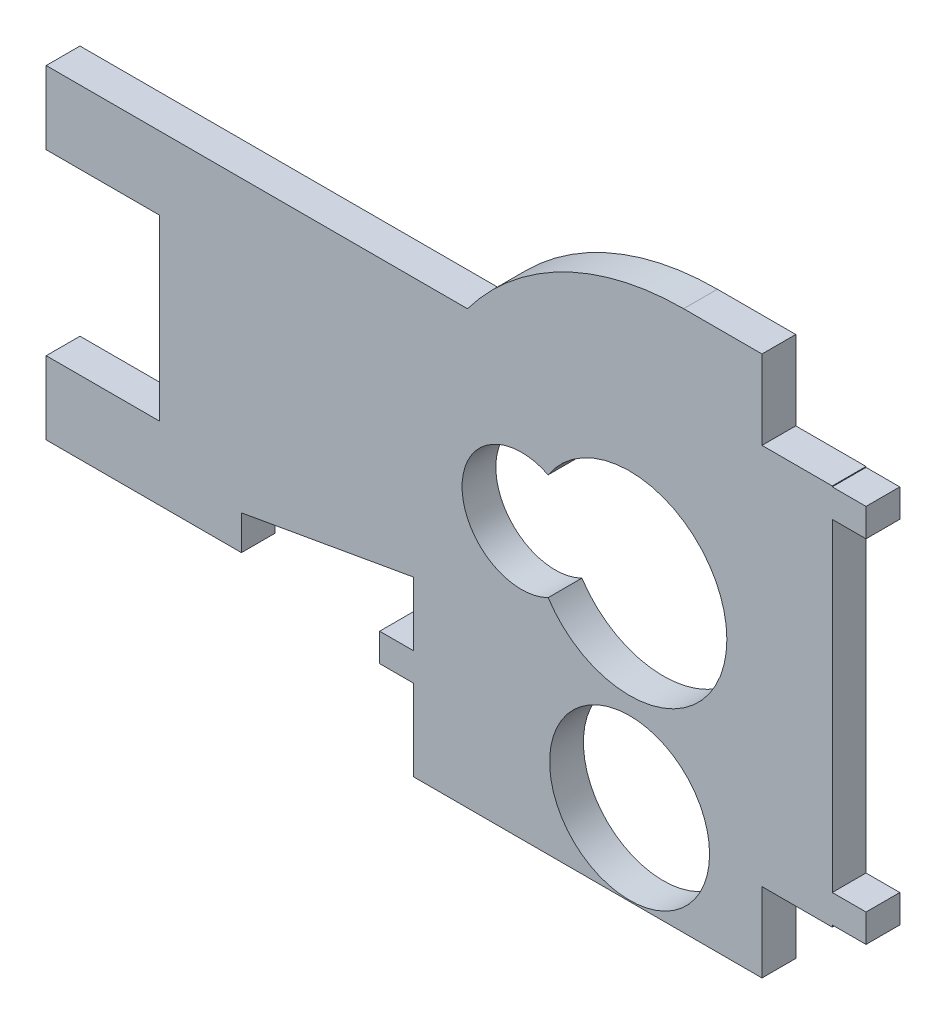
SolidWorks part; units mm, degrees
material "Balsa"
ref_plane "Front Plane" through (0, 0, 0) normal (0, 0, 1) x (1, 0, 0)
ref_plane "Top Plane" through (0, 0, 0) normal (0, 1, 0) x (1, 0, 0)
ref_plane "Right Plane" through (0, 0, 0) normal (1, 0, 0) x (0, 0, -1)
sketch "Sketch1" plane through (0, 0, 0) normal (0, 0, 1) x (1, 0, 0)
  line L0 (0, -1000.1535) -> (0, 48999.8465) construction
  line L1 (0, 9.144) -> (-5.08, 9.144) construction
  line L2 (-1000, 0) -> (49000, 0) construction
  line L3 (9.525, 16.51) -> (11.1125, 16.51)
  line L4 (2.54, 21.59) -> (9.525, 21.59)
  line L5 (-10.16, 8.89) -> (-10.16, -3.81)
  line L6 (-10.16, -3.81) -> (9.525, -3.81)
  line L7 (9.525, 21.59) -> (9.525, -3.81)
  line L8 (-11.7475, 0) -> (-10.16, 0)
  line L9 (-11.7475, 0) -> (-11.7475, 1.3208)
  line L10 (-11.7475, 1.3208) -> (-10.16, 1.3208)
  line L11 (-10.16, 0) -> (-10.16, 1.3208)
  line L12 (9.525, 0) -> (11.1125, 0)
  line L13 (9.525, 0) -> (9.525, 1.3208)
  line L14 (9.525, 1.3208) -> (11.1125, 1.3208)
  line L15 (11.1125, 0) -> (11.1125, 1.3208)
  line L16 (9.525, 16.51) -> (9.525, 17.8308)
  line L17 (9.525, 17.8308) -> (11.1125, 17.8308)
  line L18 (11.1125, 16.51) -> (11.1125, 17.8308)
  line L19 (-7.62, 16.51) -> (-27.4189, 16.51)
  line L20 (-27.4189, 16.51) -> (-27.4189, 1.27)
  line L21 (-27.4189, 1.27) -> (-10.16, 4.318)
  line L22 (9.525, 8.89) -> (-35.5862, 8.89) construction
  line L23 (-27.4189, 1.27) -> (-18.2418, 1.27)
  line L24 (-27.4189, 13.081) -> (-22.0849, 13.081)
  line L25 (-27.4189, 13.081) -> (-27.4189, 4.699)
  line L26 (-27.4189, 4.699) -> (-22.0849, 4.699)
  line L27 (-22.0849, 13.081) -> (-22.0849, 4.699)
  line L28 (-18.2418, 1.27) -> (-18.2418, 2.8907)
  circle A0 centre (0, 0) radius 3.7592
  arc A1 (-3.829, 6.6457) -> (-3.829, 11.6423) centre (0, 9.144) ccw
  arc A2 (-3.829, 11.6423) -> (-3.829, 6.6457) centre (-5.08, 9.144) ccw
  arc A3 (2.54, 21.59) -> (-10.16, 8.89) centre (2.54, 8.89) ccw
  point P33 (9.525, 8.89)
  point P35 (-27.4189, 8.89)
  point P41 (-27.4189, 8.89)
  dimension "D1" = 7.5184
  dimension "D4" = 3.81
  dimension "D3" = 9.144
  dimension "D5" = 2.794
  dimension "D9" = 12.7
  dimension "D10" = 1.5875
  dimension "D2" = 25.4
  dimension "D6" = 9.525
  dimension "D7" = 5.08
  dimension "D8" = 19.685
  dimension "D11" = 9.144
  dimension "D12" = 1.3208
  dimension "D13" = 1.3208
  dimension "D14" = 1.5875
  dimension "D15" = 2
  dimension "D16" = 8.128
  dimension "D17" = 15.24
  dimension "D18" = 17.526
  dimension "D19" = 8.382
  dimension "D20" = 5.334
extrude "Boss-Extrude1" add sketch "Sketch1" along normal blind 1.5875 contours L4 A3 L5 L6 L7 A0 A2 A1 | L10 L9 L8 L5 | L3 L18 L17 L7 | L12 L15 L14 L7 | A3 L19 L20 L21 L5 | L23 L28 L21 region at (10.3187, 17.1704, 0) region at (9.2036, 8.9154, 0) region at (10.3187, 0.6604, 0) region at (-17.5342, 9.9456, 0) region at (-10.9538, 0.6604, 0) region at (-21.3008, 1.8102, 0)
sketch "Sketch2" plane through (0, 0, 1.5875) normal (0, 0, 1) x (1, 0, 0)
  line L0 (9.525, -0.9144) -> (9.525, -3.0226) construction
  line L1 (6.223, -3.8481) -> (9.525, -3.8481)
  line L2 (6.223, -3.8481) -> (6.223, -0.0889)
  line L3 (6.223, -0.0889) -> (9.525, -0.0889)
  line L4 (9.525, -3.8481) -> (9.525, -0.0889)
  line L5 (9.525, -0.9144) -> (9.525, -3.0226)
  line L6 (9.525, 20.8026) -> (9.525, 18.6944) construction
  line L7 (9.525, 20.8026) -> (9.525, 18.6944)
  line L9 (6.223, 17.8689) -> (9.525, 17.8689)
  line L10 (6.223, 17.8689) -> (6.223, 21.6281)
  line L11 (6.223, 21.6281) -> (9.525, 21.6281)
  line L12 (9.525, 17.8689) -> (9.525, 21.6281)
  point P8 (9.525, -1.9685)
  point P9 (9.525, -1.9685)
  point P10 (9.525, 19.7485)
  point P15 (9.525, 19.7485)
  line M4 (9.525, 21.59) -> (2.54, 21.59)
  line M11 (-10.16, -3.81) -> (9.525, -3.81)
  line M12 (9.525, -3.81) -> (9.525, 0)
  line M20 (9.525, 17.8308) -> (9.525, 21.59)
  dimension "D1" = 3.7592
  dimension "D2" = 3.302
  dimension "D3" = 3.7592
  dimension "D4" = 3.302
extrude "Cut-Extrude1" cut sketch "Sketch2" against normal up to next contours L3 L2 L4 M11 M12 | L10 L9 M20 M4 region at (7.874, -1.9495, 1.5875) region at (7.874, 19.7294, 1.5875)
move or copy body "Body-Move/Copy1" [suppressed] bodies to move or copy 102
